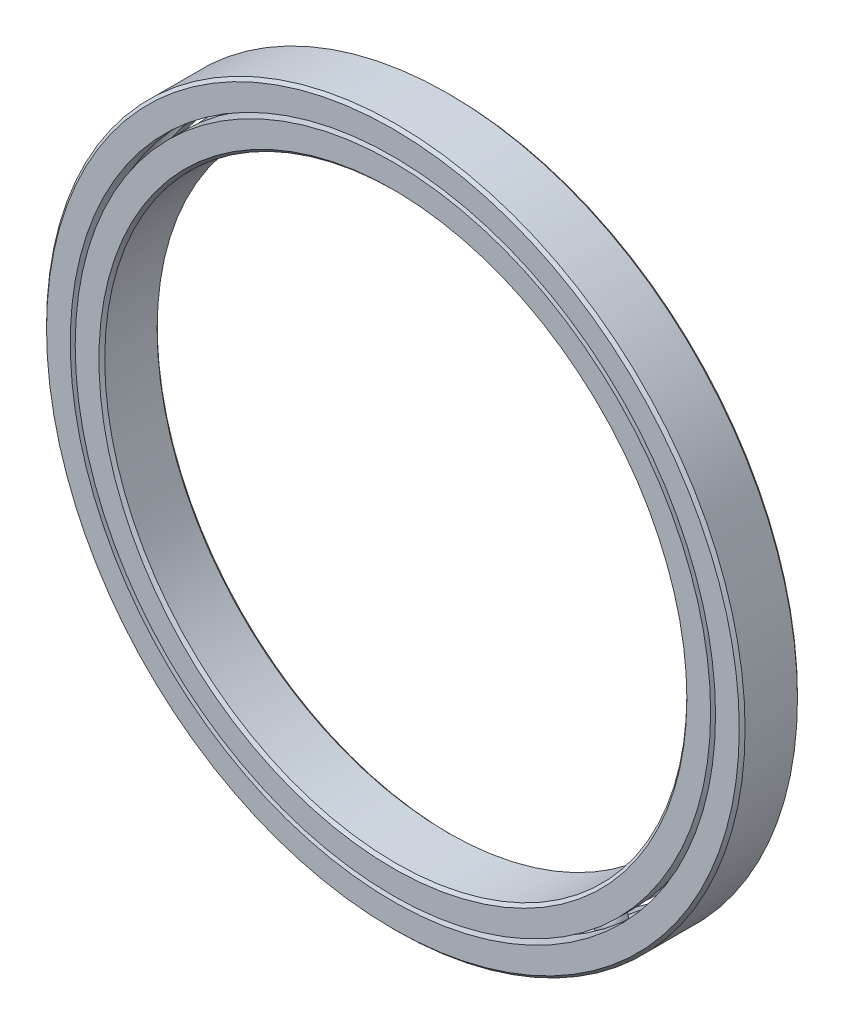
SolidWorks part; units mm, degrees
ref_plane "Front Plane" through (0, 0, 0) normal (0, 0, 1) x (1, 0, 0)
ref_plane "Top Plane" through (0, 0, 0) normal (0, 1, 0) x (1, 0, 0)
ref_plane "Right Plane" through (0, 0, 0) normal (1, 0, 0) x (0, 0, -1)
sketch "Sketch1" plane through (0, 0, 0) normal (1, 0, 0) x (0, 0, -1)
  line L0 (-3.175, 0) -> (3.175, 0) construction
  line L1 (0, 38.1) -> (0, -38.1) construction
  line L2 (2.8575, 38.1) -> (-2.8575, 38.1)
  line L3 (-2.8575, 38.1) -> (-3.175, 37.7825)
  line L4 (-3.175, 37.7825) -> (-3.175, 35.1937)
  line L5 (-3.175, 35.1937) -> (-1.4111, 35.1937)
  line L6 (3.175, 35.1937) -> (1.4111, 35.1937)
  line L7 (3.175, 37.7825) -> (3.175, 35.1937)
  line L8 (2.8575, 38.1) -> (3.175, 37.7825)
  line L9 (0, 38.1) -> (0, 34.925) construction
  line L10 (0, 34.925) -> (0, 31.75) construction
  arc A0 (-1.4111, 35.1937) -> (1.4111, 35.1937) centre (0, 34.925) cw
  point P14 (0, 31.75)
  dimension "Width" = 6.35
  dimension "OD" = 76.2
  dimension "D1" = 45
  dimension "D2" = 0.3175
  dimension "Shaft Dia" = 63.5
  dimension "D3" = 2.8222
  dimension "D4" = 0.2687
revolve "Revolve1" add sketch "Sketch1" angle 360 about L0
sketch "Sketch3" plane through (0, 0, 0) normal (1, 0, 0) x (0, 0, -1)
  line L0 (-3.175, 34.6563) -> (-1.4111, 34.6563)
  line L1 (0, 38.1) -> (0, -38.1) construction
  line L2 (-3.175, 37.7825) -> (-3.175, 35.1937) construction
  line L3 (-3.175, 34.6563) -> (-3.175, 32.0675)
  line L4 (-2.8575, 38.1) -> (-3.175, 37.7825) construction
  line L5 (-3.175, 32.0675) -> (-2.8575, 31.75)
  line L6 (-2.8575, 31.75) -> (2.8575, 31.75)
  line L7 (2.8575, 38.1) -> (2.8575, -38.1) construction
  line L8 (2.8575, 31.75) -> (3.175, 32.0675)
  line L9 (3.175, -37.7825) -> (3.175, 37.7825) construction
  line L10 (3.175, 32.0675) -> (3.175, 34.6563)
  line L11 (3.175, 34.6563) -> (1.4111, 34.6563)
  line L13 (2.8575, 38.1) -> (3.175, 37.7825) construction
  arc A0 (1.4111, 35.1937) -> (-1.4111, 35.1937) centre (0, 34.925) ccw construction
  arc A1 (1.4111, 34.6563) -> (-1.4111, 34.6563) centre (0, 34.925) cw
revolve "Revolve3" add sketch "Sketch3" angle 360 about L0
sketch "Sketch4" plane through (0, 0, 0) normal (1, 0, 0) x (0, 0, -1)
  line L0 (-1.4365, 34.925) -> (1.4365, 34.925)
  arc A2 (-1.4365, 34.925) -> (1.4365, 34.925) centre (0, 34.925) cw
  arc A3 (1.4111, 35.1937) -> (-1.4111, 35.1937) centre (0, 34.925) ccw construction
revolve "Revolve4" add sketch "Sketch4" angle 360 about L0
ref_axis "Axis1" through (0, 0, -3.175) along (0, 0, 1)
pattern_circular "CirPattern1" count 10 every 36 about axis through (0, 0, -3.175) along (0, 0, 1) of bodies 104
equation "\"D2@Sketch1\" = \"Width@Sketch1\"*.05"
equation "\"D3@Sketch1\" = \"Width@Sketch1\"/2.25"
equation "\"D4@Sketch1\" = (((\"OD@Sketch1\"-\"Width@Sketch1\")/2)/3.25)*.025"
equation "\"D2@CirPattern1\" = 360/\"Balls@CirPattern1\""
